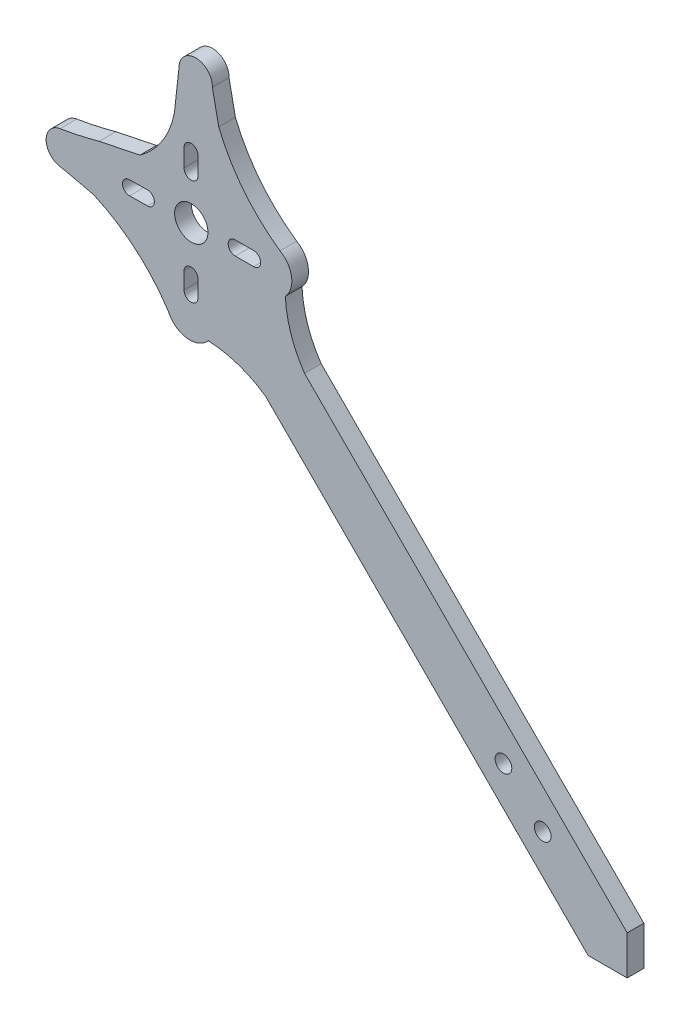
SolidWorks part; units mm, degrees
ref_plane "Front Plane" through (0, 0, 0) normal (0, 0, 1) x (1, 0, 0)
ref_plane "Top Plane" through (0, 0, 0) normal (0, 1, 0) x (1, 0, 0)
ref_plane "Right Plane" through (0, 0, 0) normal (1, 0, 0) x (0, 0, -1)
sketch "Sketch1" plane through (0, 0, 0) normal (0, 0, 1) x (1, 0, 0)
  line L0 (-10.7209, -18.1077) -> (-10.7209, -14.881) construction
  line L11 (-11.9775, -18.1077) -> (-11.9775, -14.881)
  line L18 (-9.4643, -18.1077) -> (-9.4643, -14.881)
  line L27 (-10.7209, -34.1513) -> (-10.7209, -37.134) construction
  line L34 (-11.9775, -34.1513) -> (-11.9775, -37.134)
  line L41 (-9.4643, -34.1513) -> (-9.4643, -37.134)
  line L42 (-2.7753, -25.9618) -> (0.5508, -25.9618) construction
  line L52 (-2.7753, -24.7052) -> (0.5508, -24.7052)
  line L57 (-2.7753, -27.2184) -> (0.5508, -27.2184)
  line L59 (-18.5751, -26.0533) -> (-21.8015, -26.0906) construction
  line L60 (-18.5896, -24.7967) -> (-21.816, -24.8341)
  line L66 (-18.5605, -27.3098) -> (-21.7869, -27.3471)
  line L69 (-31.1251, -29.7267) -> (-28.2426, -30.4119)
  line L72 (-6.8797, -2.9874) -> (-5.7307, -8.5844)
  line L75 (-27.2491, -21.5861) -> (-19.907, -20.0553)
  line L83 (60.733, -104.4759) -> (67.7793, -104.4759)
  line L86 (9.7067, -39.2772) -> (67.7793, -97.4402)
  line L89 (2.6588, -46.3145) -> (60.733, -104.4759)
  line L92 (67.7793, -97.4402) -> (67.7793, -104.4759)
  line L100 (-13.6983, -10.2571) -> (-12.8769, -2.8022)
  circle A104 centre (52.5748, -89.2575) radius 1.5
  arc A106 (-11.9775, -18.1077) -> (-9.4643, -18.1077) centre (-10.7209, -18.1077) ccw
  arc A107 (-9.4643, -14.881) -> (-11.9775, -14.881) centre (-10.7209, -14.881) ccw
  arc A108 (-11.9775, -34.1513) -> (-9.4643, -34.1513) centre (-10.7209, -34.1513) cw
  arc A109 (-9.4643, -37.134) -> (-11.9775, -37.134) centre (-10.7209, -37.134) cw
  circle A110 centre (-10.6752, -26.0075) radius 3
  arc A111 (-2.7753, -24.7052) -> (-2.7753, -27.2184) centre (-2.7753, -25.9618) ccw
  arc A112 (0.5508, -27.2184) -> (0.5508, -24.7052) centre (0.5508, -25.9618) ccw
  arc A113 (-18.5896, -24.7967) -> (-18.5605, -27.3098) centre (-18.5751, -26.0533) cw
  arc A114 (-21.7869, -27.3471) -> (-21.816, -24.8341) centre (-21.8015, -26.0906) cw
  arc A115 (-14.8011, -41.8588) -> (-7.6351, -42.842) centre (-10.9165, -40.1522) ccw
  arc A116 (5.2959, -22.3729) -> (6.2496, -28.9782) centre (3.1788, -26.0501) cw
  arc A117 (-28.2426, -30.4119) -> (-14.8011, -41.8588) centre (-40.7861, -58.7564) cw
  arc A118 (-5.7307, -8.5844) -> (5.2959, -22.3729) centre (22.9875, 3.0782) ccw
  arc A119 (-34.3567, -29.0388) -> (-34.2924, -23.1311) centre (-33.8015, -26.0906) cw
  arc A120 (-6.8797, -2.9874) -> (-12.8769, -2.8022) centre (-9.8783, -2.8948) ccw
  arc A121 (-34.3567, -29.0388) -> (-31.1251, -29.7267) centre (-47.3126, -97.8294) cw
  arc A122 (-34.2924, -23.1311) -> (-27.2491, -21.5861) centre (-45.7484, 45.9252) ccw
  arc A123 (-19.907, -20.0553) -> (-13.6983, -10.2571) centre (-28.8074, -7.5492) ccw
  arc A124 (-7.6351, -42.842) -> (2.6588, -46.3145) centre (-8.604, -62.7079) cw
  arc A125 (6.2496, -28.9782) -> (9.7067, -39.2772) centre (26.117, -28.039) ccw
  circle A126 centre (45.5091, -82.1812) radius 1.5
  point P4 (-10.7209, -16.4944)
  point P13 (-10.7209, -35.6427)
  point P21 (-1.1123, -25.9618)
  point P28 (-20.1883, -26.0719)
  dimension "D1" = 10
extrude "Boss-Extrude1" add sketch "Sketch1" along normal blind 3
